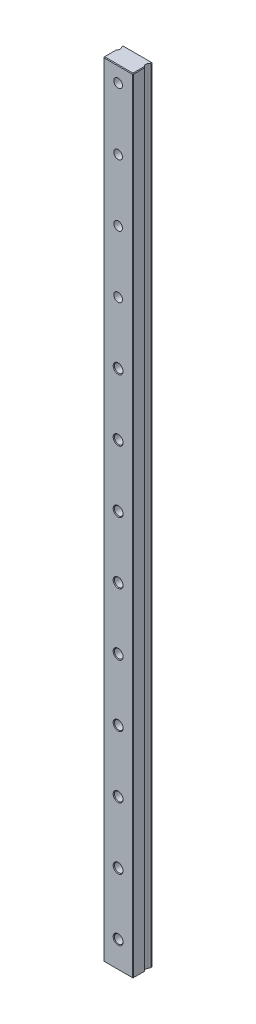
SolidWorks part; units mm, degrees
material "Chrome Stainless Steel"
ref_plane "Front" through (0, 0, 0) normal (0, 0, 1) x (1, 0, 0)
ref_plane "Top" through (0, 0, 0) normal (0, 1, 0) x (1, 0, 0)
ref_plane "Right" through (0, 0, 0) normal (1, 0, 0) x (0, 0, -1)
sketch "Sketch1" plane through (0, 0, 0) normal (0, 1, 0) x (1, 0, 0)
  line L0 (-6, 4) -> (-6, 2.75)
  line L1 (-6, 4) -> (6, 4)
  line L2 (-6, 4) -> (-6, -4)
  line L3 (-6, -4) -> (6, -4)
  line L4 (6, 4) -> (6, -4)
  line L5 (-6, 4) -> (6, -4) construction
  line L6 (-6, -4) -> (6, 4) construction
  line L7 (6, 4) -> (6, 2)
  line L8 (-6.75, 2) -> (6.75, 2) construction
  circle A0 centre (-6, 2) radius 0.75 construction
  circle A1 centre (6, 2) radius 0.75 construction
  arc A2 (-6, 0.701) -> (-6, 3.299) centre (-6.75, 2) ccw
  arc A3 (6, 3.299) -> (6, 0.701) centre (6.75, 2) ccw
  point P0 (0, 0)
  dimension "D1" = 8
  dimension "D2" = 12
extrude "Boss-Extrude1" add sketch "Sketch1" along normal blind 317 contours A3 L4 L1 L0 A2 L2 L3 region at (0, 0, 0.0593)
sketch "Sketch3" plane through (0, 0, -4) normal (0, 0, -1) x (-1, 0, 0)
  line L0 (6, 317) -> (6, 0) construction
  line L1 (-6, 0) -> (6, 0) construction
  line L2 (-6, 0) -> (-6, 10.75) construction
  line L3 (-6, 10.75) -> (6, 10.75) construction
  line L4 (6, 0) -> (6, 10.75) construction
  line L5 (-6, 0) -> (6, 10.75) construction
  line L6 (-6, 10.75) -> (6, 0) construction
  circle A0 centre (0, 10.75) radius 3.25
  circle A1 centre (0, 10.75) radius 1.75
  circle A2 centre (0, 35.75) radius 3.25
  circle A3 centre (0, 35.75) radius 1.75
  circle A4 centre (0, 60.75) radius 3.25
  circle A5 centre (0, 60.75) radius 1.75
  circle A6 centre (0, 85.75) radius 3.25
  circle A7 centre (0, 85.75) radius 1.75
  circle A8 centre (0, 110.75) radius 3.25
  circle A9 centre (0, 110.75) radius 1.75
  circle A10 centre (0, 135.75) radius 3.25
  circle A11 centre (0, 135.75) radius 1.75
  circle A12 centre (0, 160.75) radius 3.25
  circle A13 centre (0, 160.75) radius 1.75
  circle A14 centre (0, 185.75) radius 3.25
  circle A15 centre (0, 185.75) radius 1.75
  circle A16 centre (0, 210.75) radius 3.25
  circle A17 centre (0, 210.75) radius 1.75
  circle A18 centre (0, 235.75) radius 3.25
  circle A19 centre (0, 235.75) radius 1.75
  circle A20 centre (0, 260.75) radius 3.25
  circle A21 centre (0, 260.75) radius 1.75
  circle A22 centre (0, 285.75) radius 3.25
  circle A23 centre (0, 285.75) radius 1.75
  circle A24 centre (0, 310.75) radius 3.25
  circle A25 centre (0, 310.75) radius 1.75
  circle A26 centre (0, 335.75) radius 3.25
  circle A27 centre (0, 335.75) radius 1.75
  point P4 (0, 5.375)
  dimension "D1" = 14
extrude "Cut-Extrude3" cut sketch "Sketch3" against normal blind 8.5 contours A27 | A25 | A23 | A21 | A19 | A17 | A15 | A13 | A9 | A7 | A5 | A3 | A11 | A1 region at (0, 35.75, -4) region at (0, 60.75, -4) region at (0, 85.75, -4) region at (0, 110.75, -4) region at (0, 160.75, -4) region at (0, 185.75, -4) region at (0, 210.75, -4) region at (0, 235.75, -4) region at (0, 260.75, -4) region at (0, 285.75, -4) region at (0, 310.75, -4) region at (0, 335.75, -4)
extrude "Cut-Extrude4" cut sketch "Sketch3<6>" against normal blind 4.5
sketch "Sketch3<6>" plane through (0, 0, -4) normal (0, 0, -1) x (-1, 0, 0) same geometry as "Sketch3"
chamfer "Chamfer3" distance 0.25 angle 45 43 edges at (-1.75, 210.75, 4) (-1.75, 185.75, 4) (-1.75, 160.75, 4) (-1.75, 135.75, 4) (-1.75, 110.75, 4) (-1.75, 85.75, 4) (-1.75, 60.75, 4) (-1.75, 35.75, 4) (-1.75, 10.75, 4) (0, 0, 4) (6, 0, 1.6495) (-6, 0, 1.6495) (6, 317, 1.6495) (-6, 317, 1.6495) (6, 158.5, 4) (0, 317, 4) (-6, 158.5, 4) (6, 0, -3.6495) (-6, 0, -3.6495) (0, 0, -4) (6, 317, -3.6495) (-6, 317, -3.6495) (-6, 158.5, -4) (0, 317, -4) (6, 158.5, -4) (-3.25, 210.75, -4) (-1.75, 210.75, 0.5) (-3.25, 185.75, -4) (-1.75, 185.75, 0.5) (-3.25, 160.75, -4) (-1.75, 160.75, 0.5) (-3.25, 135.75, -4) (-1.75, 135.75, 0.5) (-3.25, 110.75, -4) (-1.75, 110.75, 0.5) (-3.25, 85.75, -4) (-1.75, 85.75, 0.5) (-3.25, 60.75, -4) (-1.75, 60.75, 0.5) (-3.25, 35.75, -4) (-1.75, 35.75, 0.5) (-3.25, 10.75, -4) (-1.75, 10.75, 0.5)
